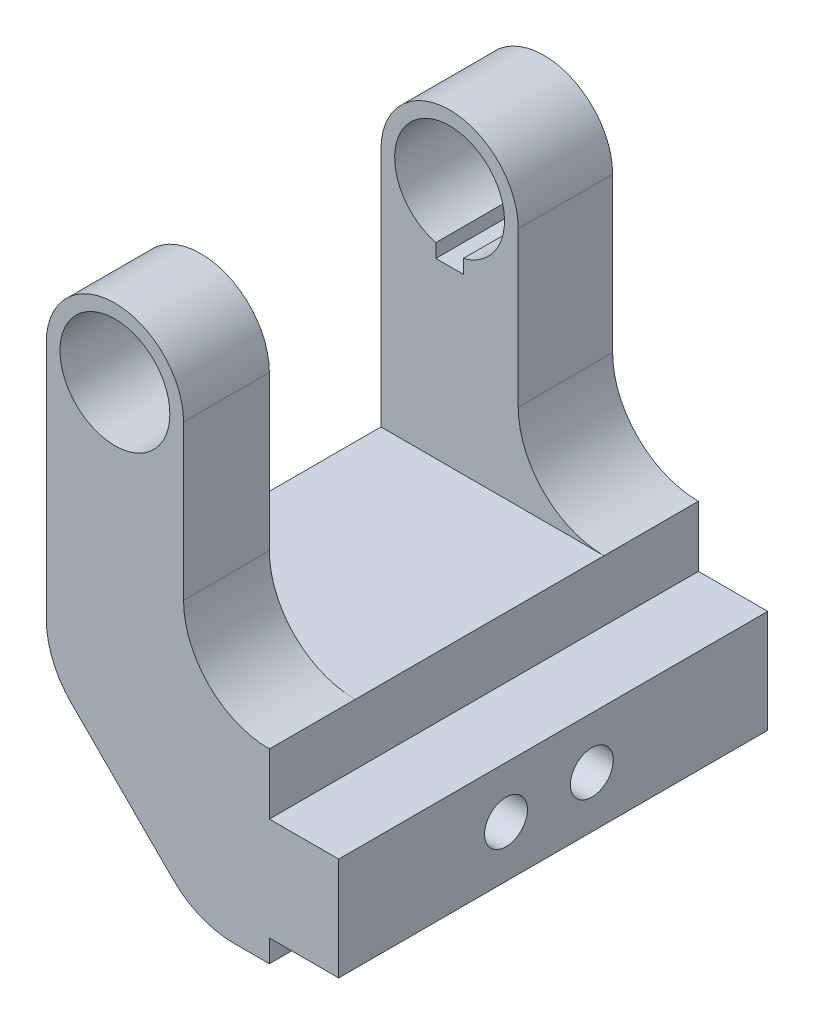
SolidWorks part; units mm, degrees
ref_plane "Front" through (0, 0, 0) normal (0, 0, 1) x (1, 0, 0)
ref_plane "Top" through (0, 0, 0) normal (0, 1, 0) x (1, 0, 0)
ref_plane "Right" through (0, 0, 0) normal (1, 0, 0) x (0, 0, -1)
sketch "Sketch1" plane through (0, 0, 0) normal (0, 0, 1) x (1, 0, 0)
  circle A0 centre (0, 0) radius 6.4
  circle A1 centre (0, 0) radius 12
extrude "Boss-Extrude1" add sketch "Sketch1" along normal blind 50
sketch "Sketch2" plane through (0, 0, 50) normal (0, 0, 1) x (1, 0, 0)
  circle A0 centre (0, 0) radius 8
  circle A1 centre (0, 0) radius 12
extrude "Cut-Extrude1" cut sketch "Sketch2" against normal through all both and the other way through all
sketch "Sketch3" plane through (0, 0, 50) normal (0, 0, 1) x (1, 0, 0)
  line L0 (-8, 0) -> (-8, -32)
  line L1 (-8, -32) -> (9.6777, -49.6777)
  line L3 (26.0762, -47.0762) -> (26.0762, -35.0762)
  line L4 (8, 0) -> (8, -28)
  line L9 (8, -28) -> (18, -28)
  line L13 (18, -35.0762) -> (26.0762, -35.0762)
  line L14 (9.6777, -49.6777) -> (18, -49.6777)
  line L15 (18, -49.6777) -> (18, -47.0762)
  line L16 (18, -47.0762) -> (26.0762, -47.0762)
  line L17 (18, -28) -> (18, -35.0762)
  circle A0 centre (0, 0) radius 8 construction
  arc A2 (-8, 0) -> (8, 0) centre (0, 0) ccw
  point P16 (0, 0)
  point P17 (0, 0)
extrude "Boss-Extrude2" add sketch "Sketch3" against normal through all
sketch "Sketch4" plane through (26.0762, 0, 0) normal (1, 0, 0) x (0, 0, -1)
  line L0 (-40, -28) -> (-40, 14.0341)
  line L1 (0, -28) -> (-50, -28) construction
  line L2 (-40, 14.0341) -> (-11, 14.0341)
  line L3 (-11, 14.0341) -> (-11, -28)
  line L4 (-11, -28) -> (-40, -28)
  line L5 (-50, 8) -> (-50, 0) construction
  dimension "D1" = 10
  dimension "D2" = 0
extrude "Cut-Extrude2" cut sketch "Sketch4" against normal through all
sketch "Sketch8" plane through (26.0762, 0, 0) normal (1, 0, 0) x (0, 0, -1)
  line L0 (-25.5, -41.0762) -> (-25.5, -40.4739) construction
  line L1 (0, -47.0762) -> (0, -35.0762) construction
  circle A0 centre (-30.5, -41.0762) radius 2.5
  circle A1 centre (-20.5, -41.0762) radius 2.5
  point P2 (0, -41.0762)
  point P3 (-25.5, -31.0762)
  point P9 (-25.5, -31.0762)
  dimension "D1" = 5
extrude "Cut-Extrude6" cut sketch "Sketch8" against normal through all both and the other way through all
sketch "Sketch9" plane through (26.0762, 0, 0) normal (1, 0, 0) x (0, 0, -1)
  line L0 (-20.5, -36.0762) -> (-30.5, -36.0762)
  line L1 (-30.5, -46.0762) -> (-20.5, -46.0762)
  circle A0 centre (-30.5, -41.0762) radius 5 construction
  circle A1 centre (-20.5, -41.0762) radius 5 construction
  arc A2 (-30.5, -36.0762) -> (-30.5, -46.0762) centre (-30.5, -41.0762) ccw
  arc A3 (-20.5, -46.0762) -> (-20.5, -36.0762) centre (-20.5, -41.0762) ccw
extrude "Cut-Extrude9" cut sketch "Sketch9" against normal blind 20 from offset 10 offset against normal yes
sketch "Sketch10" plane through (0, 0, 0) normal (0, 0, -1) x (-1, 0, 0)
  line L0 (0, 9.5754) -> (0, 0) construction
  line L5 (0, 0) -> (13.3414, 0) construction
  line L6 (1.6, -7.7968) -> (1.6, -6.1968)
  line L7 (-1.6, -7.7968) -> (1.6, -7.7968)
  line L8 (-1.6, -6.1968) -> (-1.6, -7.7968)
  line L9 (1.6, -6.1968) -> (-1.6, -6.1968)
extrude "Cut-Extrude10" cut sketch "Sketch10" against normal blind 20
fillet "Fillet1" radius 10 4 edges at (8, -28, 5.5) (8, -28, 45) (-8, -32, 25) (9.6777, -49.6777, 25)
